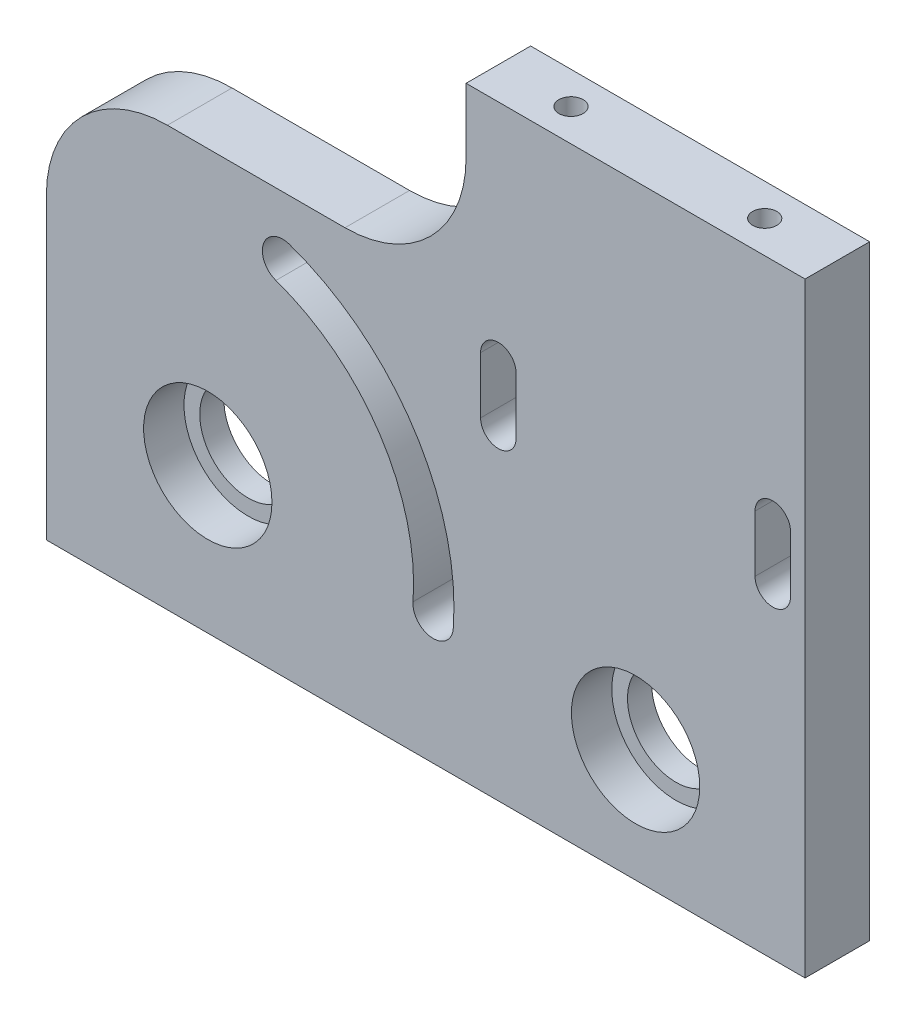
SolidWorks part; units mm, degrees
material "Alliage 1060"
ref_plane "Plan de face" through (0, 0, 0) normal (0, 0, 1) x (1, 0, 0)
ref_plane "Plan de dessus" through (0, 0, 0) normal (0, 1, 0) x (1, 0, 0)
ref_plane "Plan de droite" through (0, 0, 0) normal (1, 0, 0) x (0, 0, -1)
sketch "Esquisse1" plane through (0, 0, 0) normal (0, 0, 1) x (1, 0, 0)
  line L1 (0, 0) -> (114.433, 0)
  line L2 (0, 0) -> (0, 75)
  line L3 (0, 75) -> (114.433, 75)
  line L4 (114.433, 0) -> (114.433, 75)
  dimension "D1" = 75
extrude "Boss.-Extru.1" add sketch "Esquisse1" along normal blind 8
sketch "Esquisse2" plane through (0, 0, 8) normal (0, 0, 1) x (1, 0, 0)
  line L0 (20, 18) -> (20, 0) construction
  line L1 (0, 0) -> (114.433, 0) construction
  line L2 (20, 18) -> (0, 18) construction
  line L3 (0, 75) -> (0, 0) construction
  line L4 (20, 18) -> (73, 14) construction
  circle A0 centre (20, 18) radius 7.95
  circle A1 centre (73, 14) radius 7.95
  dimension "D1" = 15.9
  dimension "D2" = 18
  dimension "D3" = 20
  dimension "D4" = 53
  dimension "D5" = 14
extrude "Enlèv. mat.-Extru.1" cut sketch "Esquisse2" against normal blind 5
sketch "Esquisse3" plane through (0, 0, 3) normal (0, 0, 1) x (1, 0, 0)
  circle A0 centre (20, 18) radius 6
  circle A1 centre (73, 14) radius 6
  dimension "D1" = 12
extrude "Enlèv. mat.-Extru.2" cut sketch "Esquisse3" against normal up to next
sketch "Esquisse4" plane through (0, 0, 8) normal (0, 0, 1) x (1, 0, 0)
  line L0 (20, 18) -> (47.9206, 15.8928) construction
  line L1 (47.9206, 15.8928) -> (73, 14) construction
  line L2 (20, 18) -> (29.2618, 44.4238) construction
  arc A0 (29.2618, 44.4238) -> (47.9206, 15.8928) centre (20, 18) cw construction
  arc A1 (50.4135, 15.7046) -> (30.0887, 46.7831) centre (20, 18) ccw
  arc A2 (45.4277, 16.0809) -> (28.4348, 42.0646) centre (20, 18) ccw
  arc A3 (45.4277, 16.0809) -> (50.4135, 15.7046) centre (47.9206, 15.8928) ccw
  arc A4 (30.0887, 46.7831) -> (28.4348, 42.0646) centre (29.2618, 44.4238) ccw
  point P7 (43.4337, 33.3252)
  dimension "D4" = 2.5
  dimension "D2" = 75
  dimension "D3" = 28
extrude "Enlèv. mat.-Extru.3" cut sketch "Esquisse4" against normal through all
sketch "Esquisse5" plane through (0, 0, 8) normal (0, 0, 1) x (1, 0, 0)
  line L0 (114.433, 75) -> (0, 75) construction
  line L1 (114.433, 0) -> (94, 0)
  line L2 (114.433, 0) -> (114.433, 75)
  line L3 (114.433, 75) -> (94, 75)
  line L4 (94, 0) -> (94, 75)
  circle A0 centre (73, 14) radius 6 construction
  dimension "D1" = 21
extrude "Enlèv. mat.-Extru.4" cut sketch "Esquisse5" against normal through all
sketch "Esquisse6" plane through (0, 0, 8) normal (0, 0, 1) x (1, 0, 0)
  line L0 (56, 40) -> (90, 40) construction
  line L1 (0, 0) -> (94, 0) construction
  line L2 (94, 75) -> (94, 0) construction
  line L3 (90, 40) -> (90, 47) construction
  line L4 (87.8, 40) -> (87.8, 47)
  line L5 (92.2, 40) -> (92.2, 47)
  line L6 (73, 40) -> (73, 42.9196) construction
  line L7 (56, 40) -> (56, 47) construction
  line L8 (58.2, 40) -> (58.2, 47)
  line L9 (53.8, 40) -> (53.8, 47)
  arc A2 (87.8, 40) -> (92.2, 40) centre (90, 40) ccw
  arc A3 (92.2, 47) -> (87.8, 47) centre (90, 47) ccw
  arc A4 (58.2, 40) -> (53.8, 40) centre (56, 40) cw
  arc A5 (53.8, 47) -> (58.2, 47) centre (56, 47) cw
  point P1 (90, 43.5)
  point P15 (56, 43.5)
  dimension "D3" = 4.4
  dimension "D1" = 40
  dimension "D2" = 4
  dimension "D4" = 34
  dimension "D5" = 7
extrude "Enlèv. mat.-Extru.5" cut sketch "Esquisse6" against normal through all
sketch "Esquisse7" plane through (0, 0, 8) normal (0, 0, 1) x (1, 0, 0)
  line L0 (0, 75) -> (0, 0) construction
  line L1 (52, 75) -> (0, 75)
  line L2 (52, 75) -> (52, 52)
  line L3 (52, 52) -> (0, 52)
  line L4 (0, 75) -> (0, 52)
  line L5 (94, 75) -> (94, 0) construction
  line L6 (0, 0) -> (94, 0) construction
  line L7 (94, 75) -> (0, 75) construction
  dimension "D1" = 42
  dimension "D2" = 52
extrude "Enlèv. mat.-Extru.6" cut sketch "Esquisse7" against normal through all
sketch "Esquisse10" plane through (0, 75, 0) normal (0, 1, 0) x (1, 0, 0)
  line L0 (85, -4) -> (61, -4) construction
  line L1 (94, 0) -> (94, -8) construction
  circle A0 centre (85, -4) radius 1.5
  circle A1 centre (61, -4) radius 1.5
  point P6 (94, -4)
  dimension "D1" = 3
  dimension "D2" = 24
  dimension "D3" = 9
extrude "Enlèv. mat.-Extru.7" cut sketch "Esquisse10" against normal blind 30
fillet "Congé1" radius 15 2 edges at (52, 52, 4) (0, 52, 4)
sketch "Esquisse11" plane through (0, 0, 0) normal (0, -1, 0) x (1, 0, 0)
  line L0 (94, 0) -> (94, 8) construction
  line L1 (6, 4) -> (88, 4) construction
  line L2 (0, 8) -> (94, 8) construction
  line L3 (0, 8) -> (0, 0) construction
  circle A0 centre (6, 4) radius 1.5
  circle A1 centre (88, 4) radius 1.5
  point P8 (47, 8)
  point P9 (47, 4)
  point P12 (0, 4)
  dimension "D1" = 3
  dimension "D2" = 6
extrude "Enlèv. mat.-Extru.8" cut sketch "Esquisse11" against normal blind 20
